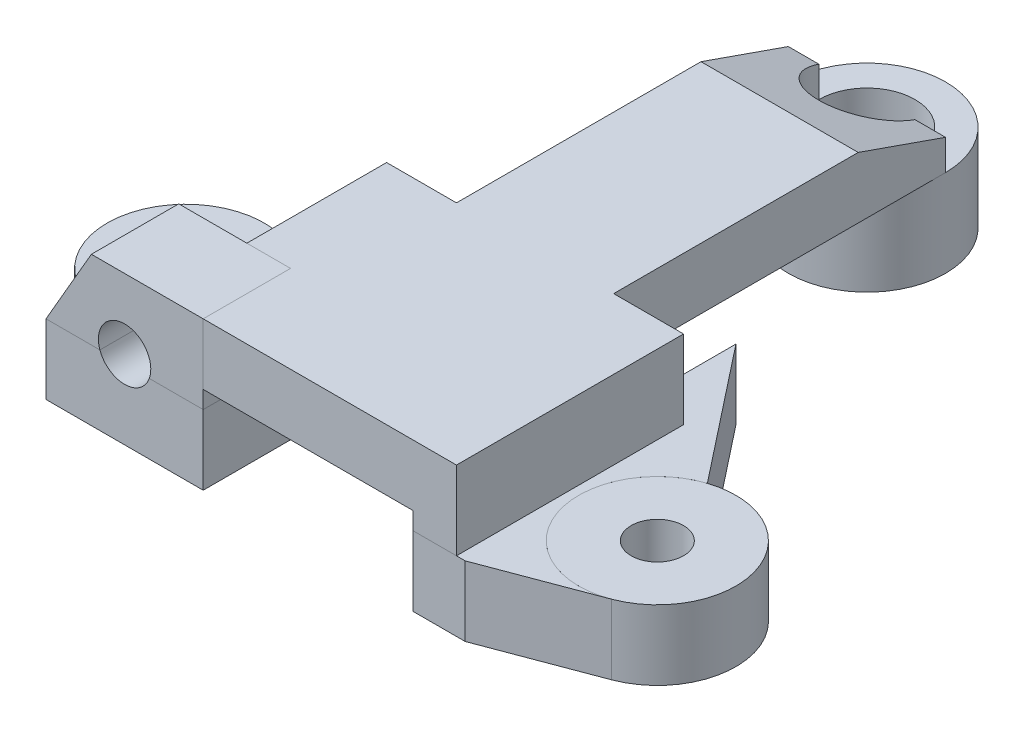
SolidWorks part; units mm, degrees
ref_plane "Front" through (0, 0, 0) normal (0, 0, 1) x (1, 0, 0)
ref_plane "Top" through (0, 0, 0) normal (0, 1, 0) x (1, 0, 0)
ref_plane "Right" through (0, 0, 0) normal (1, 0, 0) x (0, 0, -1)
sketch "Эскиз1" plane through (0, 0, 0) normal (0, 1, 0) x (1, 0, 0)
  line L0 (0, 4.033) -> (0, -32.3169) construction
  circle A0 centre (0, 0) radius 1.5
  circle A1 centre (-13.5, -25.5) radius 1.5
  circle A2 centre (13.5, -25.5) radius 1.5
  circle A3 centre (0, 0) radius 4.5
  circle A4 centre (13.5, -25.5) radius 4.5
  circle A5 centre (-13.5, -25.5) radius 4.5
  circle A8 centre (13.5, -25.5) radius 1.5 construction
  dimension "D1" = 3
  dimension "D2" = 9
extrude "Бобышка-Вытянуть2" add sketch "Эскиз1" along normal blind 4 contours A5 A1 | A5 | A5 | A0 A3 | A4 A2 region at (-4.3727, 0, 0) region at (9.1273, 0, 25.5) region at (-17.8727, 0, 25.5)
sketch "Эскиз2" plane through (0, 0, 0) normal (0, 1, 0) x (1, 0, 0)
  line L0 (0, -12.1667) -> (0, -77.7) construction
  line L1 (-15, -29.7426) -> (-15, -32)
  line L2 (-15, -32) -> (-6, -32)
  line L3 (-6, -32) -> (-6, -13.5)
  line L4 (-6, -13.5) -> (-12.0902, -21.2265)
  line L5 (-6, -7.7) -> (-6, -22.7) construction
  circle A0 centre (-13.5, -25.5) radius 4.5 construction
  arc A1 (-12.0902, -21.2265) -> (-15, -29.7426) centre (-13.5, -25.5) cw
  point P11 (-12.0902, -21.2265)
  dimension "D1" = 9
extrude "Бобышка-Вытянуть3" add sketch "Эскиз2" along normal blind 4
sketch "Эскиз3" plane through (0, 0, 32) normal (0, 0, 1) x (1, 0, 0)
  line L1 (-15, 0) -> (-6, 0) construction
  line L2 (-15, 4) -> (-12.4019, 8.5)
  line L3 (-15, 4) -> (-6, 4) construction
  line L4 (-12.4019, 8.5) -> (-6, 8.5)
  line L5 (-6, 8.5) -> (-6, 4)
  line L6 (-6, 4) -> (-9.0858, 4)
  line L7 (-15, 4) -> (-11.9142, 4)
  circle A0 centre (-10.5, 4.5) radius 1.5
  point P4 (-10.5, 0)
  line M7 (-6, 4) -> (-15, 4)
  dimension "D1" = 3
  dimension "D2" = 4.5
  dimension "D3" = 4
  dimension "D4" = 60
extrude "Бобышка-Вытянуть4" add sketch "Эскиз3" against normal blind 5 separate body contours A0 L5 L4 L2 M7 | A0 M7 region at (-9.7835, 6.334, 32) region at (-10.5, 4.8767, 32)
sketch "Эскиз4" plane through (0, 0, 32) normal (0, 0, 1) x (1, 0, 0)
  line L0 (-15, 0) -> (-6, 0) construction
  circle A0 centre (-10.5, 4.5) radius 1.5
  point P4 (-10.5, 0)
  line M7 (-6, 4) -> (-15, 4)
  dimension "D2" = 3
  dimension "D1" = 4.5
extrude "Вырез-Вытянуть1" cut sketch "Эскиз4" against normal blind 7 contours A0 M7 | A0 M7 region at (-10.5, 4.8767, 32) region at (-10.5, 3.5858, 32)
sketch "Эскиз5" plane through (0, 0, 0) normal (0, 1, 0) x (1, 0, 0)
  line L0 (9, -32) -> (15.084, -29.712)
  line L1 (6, -22.7) -> (6, -7.7) construction
  line L3 (15, -25.5) -> (-15, -25.5) construction
  line L4 (6, -13.5) -> (12.0902, -21.2265)
  line L5 (6, -5) -> (6, -32) construction
  line L6 (6, -17.3571) -> (6, -32)
  line L7 (6, -32) -> (9, -32)
  line L9 (0, 0) -> (0, -25.5) construction
  circle A0 centre (13.5, -25.5) radius 4.5 construction
  circle A1 centre (13.5, -25.5) radius 1.5 construction
  circle A2 centre (-13.5, -25.5) radius 1.5 construction
  arc A3 (15.084, -29.712) -> (12.0902, -21.2265) centre (13.5, -25.5) cw
  line M5 (6, -32) -> (9, -32)
  line M12 (6, -5) -> (6, -32)
extrude "Бобышка-Вытянуть5" add sketch "Эскиз5" along direction (0, 1, 0) on the side of the normal up to surface (4 mm away) separate body contours L0 A3 L4 M12 M5 region at (8.2131, 0, 24.1399) up to face at (-11.1448, 4, 26.7811)
sketch "Эскиз6" plane through (0, 4, 0) normal (0, 1, 0) x (1, 0, 0)
  circle A0 centre (0, 0) radius 1.5
  circle A1 centre (0, 0) radius 4.5
  circle A3 centre (0, 0) radius 1.5 construction
  circle A6 centre (0, 0) radius 4.5 construction
extrude "Бобышка-Вытянуть6" add sketch "Эскиз6" along normal up to surface (1 mm away)
sketch "Эскиз7" plane through (0, 4, 0) normal (0, 1, 0) x (1, 0, 0)
  line L0 (0, 0) -> (0, -58.3248) construction
  line L1 (-8.5, -27) -> (8.5, -27)
  line L2 (-8.5, -27) -> (-8.5, -19)
  line L3 (-8.5, -19) -> (8.5, -19)
  line L4 (8.5, -27) -> (8.5, -19)
  line L5 (-6, -32) -> (-6, -13.5) construction
  line L7 (-6, -27) -> (-9.0858, -27) construction
  line L9 (8.5, -27) -> (-6, -27)
  line L10 (8.5, -27) -> (8.5, -32)
  line L11 (8.5, -32) -> (-6, -32)
  line L12 (-6, -27) -> (-6, -32)
  line M5 (6, -32) -> (9, -32)
  line M9 (6, -13.5) -> (6, -32)
  dimension "D1" = 2.5
  dimension "D2" = 8
extrude "Бобышка-Вытянуть7" add sketch "Эскиз7" along normal up to surface (4.5 mm away) separate body contours L1 L4 L3 M9 | L10 L1 M9 M5 | L3 L0 L9 M9 | L9 L0 L11 M9 | L0 L3 L2 L1 | L0 L1 L12 L11 region at (3, 4, 23) region at (-4.25, 4, 23) region at (3, 4, 29.5) region at (-3, 4, 29.5) region at (7.25, 4, 23) region at (7.25, 4, 29.5) up to face at (-9.201, 8.5, 29.5)
sketch "Эскиз8" plane through (0, 5, 0) normal (0, 1, 0) x (1, 0, 0)
  line L0 (4.5, 0) -> (4.5, -19)
  line L1 (-4.5, 0) -> (-4.5, -19)
  line L2 (-8.5, -19) -> (8.5, -19) construction
  line L3 (4.5, 0) -> (1.5, 0)
  line L4 (-1.5, 0) -> (-4.5, 0)
  line L6 (4.5, -19) -> (-4.5, -19)
  circle A0 centre (0, 0) radius 4.5 construction
  circle A1 centre (0, 0) radius 1.5 construction
  arc A2 (1.5, 0) -> (-1.5, 0) centre (0, 0) cw
extrude "Бобышка-Вытянуть8" add sketch "Эскиз8" along normal up to surface (3.5 mm away) up to face at (-2, 8.5, 26)
sketch "Эскиз9" plane through (-4.5, 0, 0) normal (-1, 0, 0) x (0, 0, 1)
  line L0 (0, 6.75) -> (5, 8.5)
  line L1 (0, 8.5) -> (0, 5) construction
  line L2 (19, 8.5) -> (0, 8.5) construction
  line M3 (19, 8.5) -> (0, 8.5)
  line M4 (0, 8.5) -> (0, 5)
  dimension "D1" = 5
extrude "Вырез-Вытянуть2" cut sketch "Эскиз9" against normal through all and the other way through all contours L0 M4 M3 region at (-4.5, 7.9167, 1.6667)
sketch "Эскиз10" plane through (0, 5, 0) normal (0, 1, 0) x (1, 0, 0)
  circle A0 centre (0, 0) radius 2.75
  dimension "D1" = 5.5
extrude "Вырез-Вытянуть3" cut sketch "Эскиз10" against normal blind 7 from offset 5
sketch "Эскиз11" plane through (0, 0, 32) normal (0, 0, 1) x (1, 0, 0)
  line L1 (-6, 4) -> (6, 4)
  line L2 (-6, 4) -> (-6, 5)
  line L3 (-6, 5) -> (6, 5)
  line L4 (6, 4) -> (6, 5)
  dimension "D1" = 1
extrude "Вырез-Вытянуть4" cut sketch "Эскиз11" against normal up to surface (13 mm away) up to face at (0.5, 6.9375, 19)
